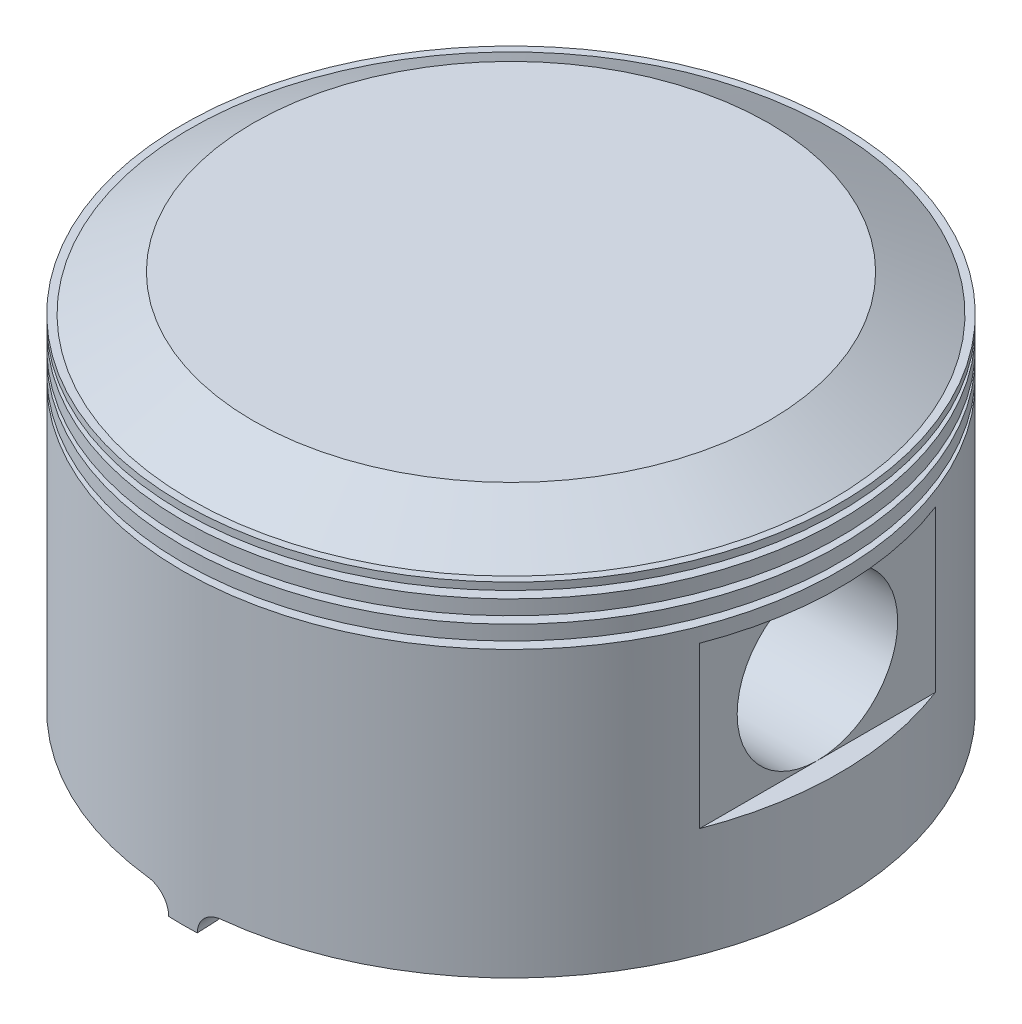
SolidWorks part; units mm, degrees
ref_plane "Front Plane" through (0, 0, 0) normal (0, 0, 1) x (1, 0, 0)
ref_plane "Top Plane" through (0, 0, 0) normal (0, 1, 0) x (1, 0, 0)
ref_plane "Right Plane" through (0, 0, 0) normal (1, 0, 0) x (0, 0, -1)
sketch "Piston CS" plane through (0, 0, 0) normal (0, 0, 1) x (1, 0, 0)
  line L0 (0, 0) -> (0, -5)
  line L1 (0, -5) -> (2.2204, -5)
  line L2 (2.2204, -5) -> (37, -25.08)
  line L3 (37, -25.08) -> (37, -35.08)
  line L4 (37, -35.08) -> (42, -35.08)
  line L5 (42, -35.08) -> (42, -52)
  line L6 (42, -52) -> (45, -52)
  line L8 (44, -5) -> (35.3397, 0)
  line L9 (35.3397, 0) -> (0, 0)
  line L10 (44, -5) -> (45, -5)
  line L12 (45, -5) -> (45, -52)
  dimension "Crown_Height" = 5
  dimension "D2" = 5
  dimension "D3" = 3
  dimension "D5" = 10
  dimension "D8" = 30
  dimension "D9" = 1
  dimension "D10" = 16.92
  dimension "Piston_Height" = 47
  dimension "D4" = 45
  dimension "D7" = 5
revolve "Revolve1" add sketch "Piston CS" angle 360 about L0
sketch "Sketch5" plane through (0, -52, 0) normal (0, -1, 0) x (1, 0, 0)
  line L0 (0, -68.5184) -> (0, 57.0205) construction
  line L1 (-73.4461, 0) -> (71.8036, 0) construction
  line L2 (-24.1039, -38) -> (-24.1039, -15)
  line L3 (-24.1039, -15) -> (-14.1039, -15)
  line L4 (-14.1039, -15) -> (-14.1039, 15)
  line L5 (-24.1039, 15) -> (-14.1039, 15)
  line L6 (-24.1039, 38) -> (-24.1039, 15)
  line L7 (24.1039, 38) -> (24.1039, 15)
  line L8 (24.1039, 15) -> (14.1039, 15)
  line L9 (14.1039, -15) -> (14.1039, 15)
  line L10 (24.1039, -15) -> (14.1039, -15)
  line L11 (24.1039, -38) -> (24.1039, -15)
  arc A2 (-24.1039, 38) -> (-24.1039, -38) centre (0, 0) ccw
  arc A3 (24.1039, 38) -> (24.1039, -38) centre (0, 0) cw
  point P10 (-14.1039, 0)
  point P19 (14.1039, 0)
  dimension "D1" = 23
  dimension "D2" = 10
  dimension "D3" = 15
extrude "Boss-Extrude1" add sketch "Sketch5" against normal up to next
sketch "Gudgeon Hole" plane through (-14.1039, 0, 0) normal (1, 0, 0) x (0, 0, -1)
  line L0 (35.3397, 0) -> (-35.3397, 0) construction
  circle A0 centre (0, -26) radius 11
  dimension "Gudgeon_Diameter" = 22
  dimension "Gudgeon_Offset" = 26
extrude "Cut-Extrude1" cut sketch "Gudgeon Hole" against normal through all and the other way through all
ref_plane "Plane1" through (0, 0, 45) normal (0, 0, 1) x (1, 0, 0)
sketch "Gudgeon Hole Cutouts" plane through (0, 0, 45) normal (0, 0, 1) x (1, 0, 0)
  line L0 (45, -37) -> (42, -37)
  line L4 (42, -35.08) -> (42, -52) construction
  line L5 (42, -37) -> (42, -15)
  line L8 (-45, -15) -> (-42, -15)
  line L9 (-42, -15) -> (-42, -37)
  line L11 (0, 0) -> (0, -52.5828) construction
  line L12 (35.3397, 0) -> (-35.3397, 0) construction
  line L14 (42, -15) -> (45, -15)
  line L15 (-42, -37) -> (-45, -37)
  spline S0 degree 2 poles (-45, -15) (-42.3111, -26) (-45, -37) knots 0 0 0 1 1 1 weights 0.034 0.045 0.056 construction
  spline S1 degree 2 poles (-45, -15) (-42.3111, -26) (-45, -37) knots 0 0 0 1 1 1 weights 0.034 0.045 0.056
  spline S2 degree 2 poles (45, -37) (42.3111, -26) (45, -15) knots 0 0 0 1 1 1 weights 0.034 0.045 0.056 construction
  spline S3 degree 2 poles (45, -37) (42.3111, -26) (45, -15) knots 0 0 0 1 1 1 weights 0.034 0.045 0.056
  dimension "D1" = 3
extrude "Cut-Extrude2" cut sketch "Gudgeon Hole Cutouts" against normal through all contours S1 L9 L8 | S3 region at (43.0861, -26, 45) region at (-43.0861, -26, 45)
sketch "Ring CS" plane through (0, 0, 0) normal (0, 0, 1) x (1, 0, 0)
  line L0 (44, -5) -> (45, -5) construction
  line L1 (45, -6) -> (43, -6)
  line L2 (45, -6) -> (45, -7)
  line L3 (45, -7) -> (43, -7)
  line L4 (43, -6) -> (43, -7)
  line L5 (45, -5) -> (45, -52) construction
  line L14 (45, -9) -> (43, -9)
  line L15 (45, -9) -> (45, -10)
  line L16 (45, -10) -> (43, -10)
  line L17 (43, -9) -> (43, -10)
  line L18 (45, -12) -> (43, -12)
  line L19 (45, -12) -> (45, -13)
  line L20 (45, -13) -> (43, -13)
  line L21 (43, -12) -> (43, -13)
  line L22 (45, -6) -> (45, -9) construction
  dimension "Groove_Offset" = 1
  dimension "Groove_Depth" = 2
  dimension "Groove_Height" = 1
  dimension "Groove_Spacing" = 3
  dimension "Num_Grooves" = 3
revolve "Cut-Revolve1" cut sketch "Ring CS" angle 360 about L0
sketch "Sketch9" plane through (0, -52, 0) normal (0, -1, 0) x (1, 0, 0)
  line L0 (0, 54.5291) -> (0, 42) construction
  line L1 (-49.8964, 0) -> (45, 0) construction
  line L2 (-1.832, 41.96) -> (-1.9629, 44.9572)
  line L3 (1.832, 41.96) -> (1.9629, 44.9572)
  line L4 (1.832, 41.96) -> (1.9629, 44.9572) construction
  line L5 (-1.832, 41.96) -> (-1.9629, 44.9572) construction
  line L6 (1.832, -41.96) -> (1.9629, -44.9572) construction
  line L7 (-1.832, -41.96) -> (-1.9629, -44.9572) construction
  line L8 (1.832, -41.96) -> (1.9629, -44.9572)
  line L9 (-1.832, -41.96) -> (-1.9629, -44.9572)
  line L10 (0, -42) -> (0, -45) construction
  arc A0 (-24.1039, -34.3948) -> (24.1039, -34.3948) centre (0, 0) ccw construction
  arc A1 (24.1039, 34.3948) -> (-24.1039, 34.3948) centre (0, 0) ccw construction
  circle A2 centre (0, 0) radius 45 construction
  arc A3 (-1.832, -41.96) -> (1.832, -41.96) centre (0, 0) ccw
  arc A4 (1.832, 41.96) -> (-1.832, 41.96) centre (0, 0) ccw
  arc A5 (-1.9629, -44.9572) -> (1.9629, -44.9572) centre (0, 0) ccw
  arc A6 (1.9629, 44.9572) -> (-1.9629, 44.9572) centre (0, 0) ccw
  dimension "D1" = 2.5
  dimension "D2" = 5
extrude "Boss-Extrude2" add sketch "Sketch9" along normal blind 3
fillet "Fillet1" radius 3 4 edges at (-1.8974, -52, 43.4586) (1.8974, -52, 43.4586) (1.8974, -52, -43.4586) (-1.8974, -52, -43.4586)
equation "\"Crown_Height@Piston CS\"=5"
equation "\"Groove_Spacing@Ring CS\"=3"
equation "\"Gudgeon_Offset@Gudgeon Hole\"= ( \"Gudgeon_Diameter@Gudgeon Hole\" / 2 ) + \"Crown_Height@Piston CS\" + \"Groove_Offset@Ring CS\" + ( \"Groove_Spacing@Ring CS\" * \"Num_Grooves@Ring CS\" )"
equation "\"Gudgeon_Diameter@Gudgeon Hole\"= 22"
equation "\"Groove_Height@Ring CS\"=1"
equation "\"Groove_Offset@Ring CS\"=1"
equation "\"Groove_Depth@Ring CS\"=2"
equation "\"Piston_Height@Piston CS\"= \"Gudgeon_Offset@Gudgeon Hole\" + ( \"Gudgeon_Diameter@Gudgeon Hole\" / 2 ) + 10"
